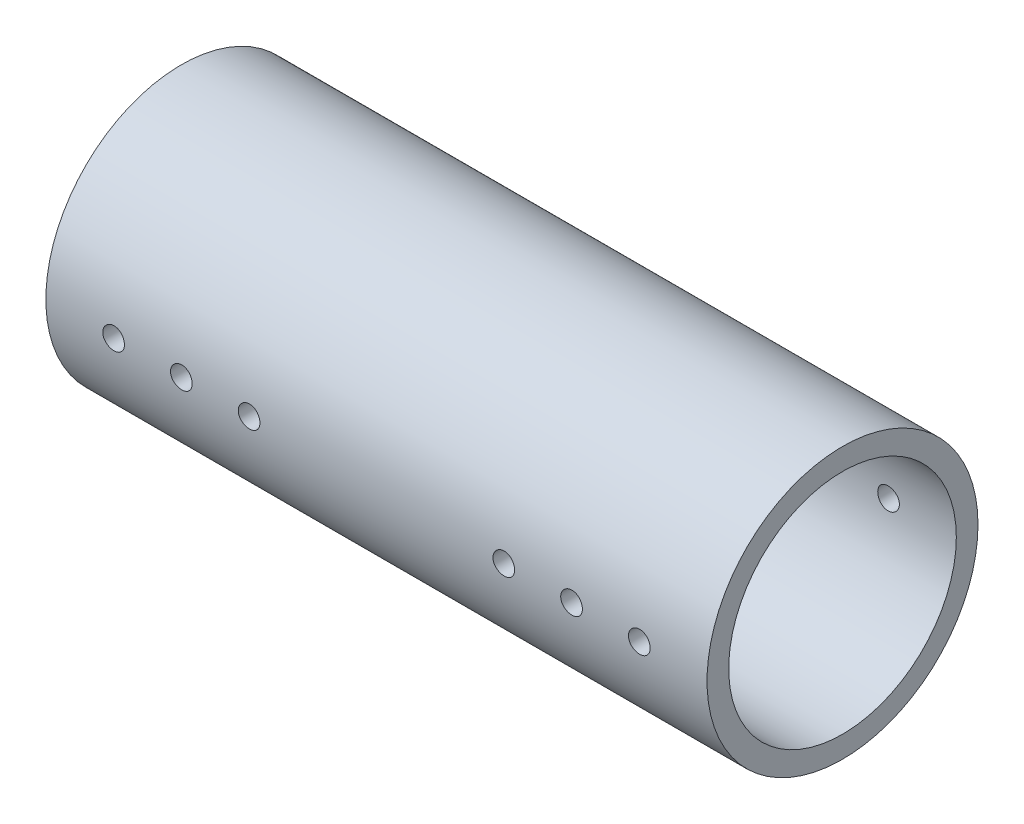
SolidWorks part; units mm, degrees
material "Zoltek Panex 33"
ref_plane "Спереди" through (0, 0, 0) normal (0, 0, 1) x (1, 0, 0)
ref_plane "Сверху" through (0, 0, 0) normal (0, 1, 0) x (1, 0, 0)
ref_plane "Справа" through (0, 0, 0) normal (1, 0, 0) x (0, 0, -1)
other "Configuration Table"
sketch "Эскиз2" plane through (0, 0, 0) normal (1, 0, 0) x (0, 0, -1)
  circle A0 centre (0, 0) radius 25
  circle A1 centre (0, 0) radius 21
  dimension "D1" = 50
  dimension "D2" = 42
extrude "Бобышка-Вытянуть2" add sketch "Эскиз2" along normal blind 122
ref_plane "Плоскость1" through (0, 0, 25) normal (0, 0, 1) x (1, 0, 0)
sketch "Эскиз4" plane through (0, 0, 25) normal (0, 0, 1) x (1, 0, 0)
  line L0 (0, -25) -> (122, -25) construction
  line L1 (122, -25) -> (122, 25) construction
  circle A0 centre (12.5, 0) radius 2
  circle A1 centre (109.5, 0) radius 2
  circle A2 centre (25, 0) radius 2
  circle A3 centre (37.5, 0) radius 2
  circle A4 centre (97, 0) radius 2
  circle A5 centre (84.5, 0) radius 2
  dimension "D1" = 4
  dimension "D4" = 4
  dimension "D6" = 4
  dimension "D8" = 4
  dimension "D10" = 4
  dimension "D11" = 4
  dimension "D2" = 12.5
  dimension "D3" = 25
  dimension "D5" = 12.5
  dimension "D7" = 12.5
  dimension "D9" = 12.5
  dimension "15" = 12.5
  dimension "D12" = 12.5
extrude "Вырез-Вытянуть2" cut sketch "Эскиз4" against normal through all and the other way blind 10 contours A0 | A1 | A2 | A3 | A5 | A4
equation "\"Diameter\"= 50мм"
equation "\"D1@Эскиз2\"= \"Diameter\""
equation "\"Length\"= 122мм"
equation "\"Thickness\"= 4мм"
equation "\"D1@Бобышка-Вытянуть2\"= \"Length\""
equation "\"D2@Эскиз2\" = \"Diameter\" - \"Thickness\" * 2"
equation "\"D4@Эскиз4\"=\"D1@Эскиз4\""
equation "\"D5@Эскиз4\"=\"D2@Эскиз4\""
equation "\"D3@Эскиз4\"=\"Diameter\"/2"
equation "\"D6@Эскиз4\"=\"D1@Эскиз4\""
equation "\"D8@Эскиз4\"=\"D6@Эскиз4\""
equation "\"D10@Эскиз4\"=\"D4@Эскиз4\""
equation "\"D11@Эскиз4\"=\"D4@Эскиз4\""
equation "\"D9@Эскиз4\"=\"D7@Эскиз4\""
